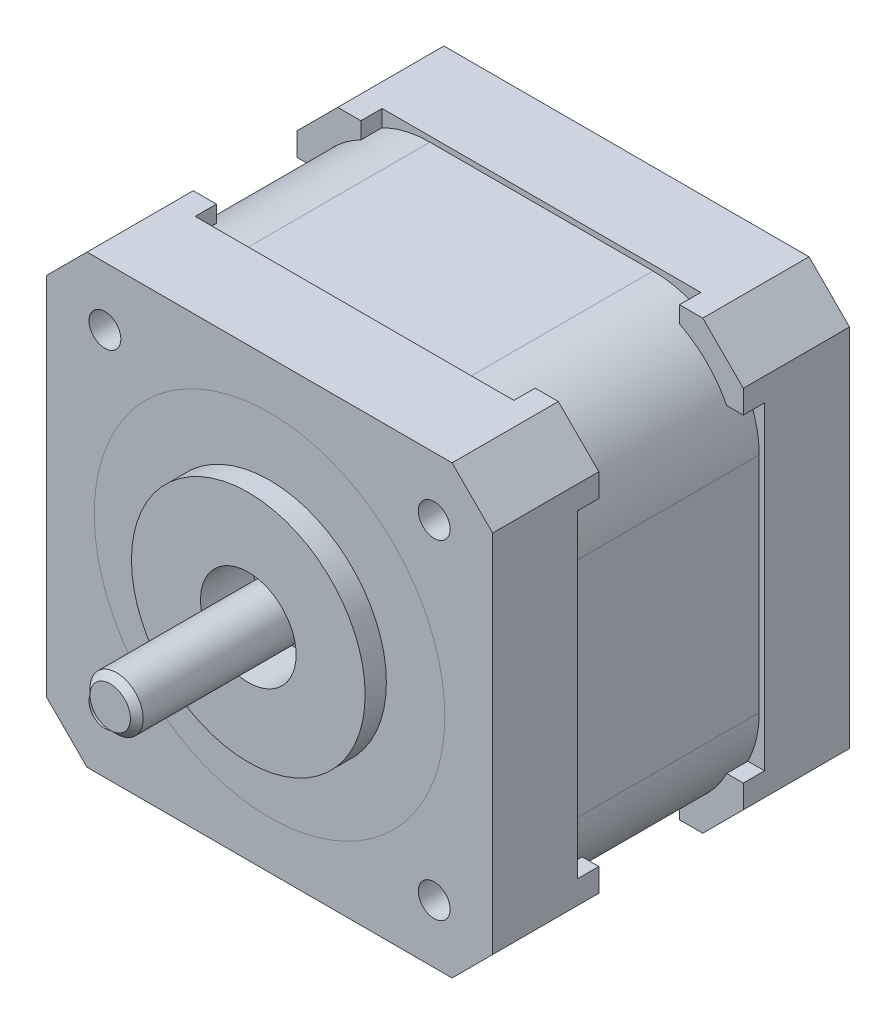
SolidWorks part; units mm, degrees
note: The reader was unsure of these and kept them because the rebuilt part matched: shared geometry of "Croquis4<4>", "Croquis5<3>", "Croquis5<4>", "Croquis5<5>".
ref_plane "Alzado" through (0, 0, 0) normal (0, 0, 1) x (1, 0, 0)
ref_plane "Planta" through (0, 0, 0) normal (0, 1, 0) x (1, 0, 0)
ref_plane "Vista lateral" through (0, 0, 0) normal (1, 0, 0) x (0, 0, -1)
sketch "Croquis1" plane through (0, 0, 0) normal (0, 0, 1) x (1, 0, 0)
  line L2 (0, 15.5) -> (-15.5, 15.5) construction
  line L3 (-15.5, -15.5) -> (-15.5, 15.5) construction
  line L4 (-17.1838, 21) -> (-21, 17.1838)
  line L5 (15.5, -15.5) -> (15.5, 15.5) construction
  line L6 (0, 21) -> (0, -21) construction
  line L7 (-21, 0) -> (21, 0) construction
  line L8 (21, 17.1838) -> (21, -17.1838)
  line L9 (17.1838, 21) -> (21, 17.1838)
  line L10 (0, -15.5) -> (-15.5, -15.5) construction
  line L11 (17.1838, -21) -> (-17.1838, -21)
  line L12 (17.1838, -21) -> (21, -17.1838)
  line L13 (-17.1838, -21) -> (-21, -17.1838)
  line L16 (17.1838, 21) -> (-17.1838, 21)
  line L18 (-21, 17.1838) -> (-21, -17.1838)
  circle A0 centre (-15.5, 15.5) radius 3
  circle A1 centre (15.5, 15.5) radius 3
  circle A2 centre (15.5, -15.5) radius 3
  circle A3 centre (-15.5, -15.5) radius 3
  point P1 (-21, 21)
  point P23 (21, 21)
  point P25 (0, 0)
  point P26 (15.5, 0)
  point P27 (-15.5, 0)
  point P34 (21, -21)
  point P35 (-21, -21)
  dimension "D4" = 6
  dimension "D2" = 31
  dimension "D3" = 15.5
  dimension "D5" = 54
  dimension "D6" = 42
  dimension "D1" = 42
extrude "Saliente-Extruir1" add sketch "Croquis1" along normal mid plane 33.6 contours L16 L4 L18 L13 L11 L12 L8 L9
sketch "Croquis2" plane through (0, 0, 16.8) normal (0, 0, 1) x (1, 0, 0)
  line L0 (21, -15) -> (-21, -15)
  line L1 (21, -15) -> (21, 15)
  line L2 (-21, -15) -> (-21, 15)
  line L3 (21, 15) -> (-21, 15)
  line L4 (21, -15) -> (-21, 15) construction
  line L5 (-21, -15) -> (21, 15) construction
  line L6 (-21, 17.1838) -> (-21, -17.1838) construction
  line L7 (17.1838, 21) -> (-17.1838, 21) construction
  line L8 (15, -21) -> (-15, -21)
  line L9 (15, -21) -> (15, 21)
  line L10 (15, 21) -> (-15, 21)
  line L11 (-15, -21) -> (-15, 21)
  line L12 (15, -21) -> (-15, 21) construction
  line L13 (15, 21) -> (-15, -21) construction
  point P1 (0, 0)
  point P3 (0, 0)
  line M10 (17.1838, 21) -> (-17.1838, 21)
  line M12 (-21, 17.1838) -> (-21, -17.1838)
  line M14 (-17.1838, -21) -> (17.1838, -21)
  line M16 (21, -17.1838) -> (21, 17.1838)
  dimension "D1" = 30
extrude "Cortar-Extruir1" cut sketch "Croquis2" against normal offset from surface (17.6 mm away) 8 from offset 8 contours L11 L3 L9 M10 | L11 L0 L9 L3 | L9 L0 L3 M16 | L11 L9 L0 M14 | L0 L11 L3 M12 up to face at (0, 0, -16.8) offset against normal yes
sketch "Croquis3" plane through (0, 0, -16.8) normal (0, 0, -1) x (-1, 0, 0)
  line L8 (-17.1838, 21) -> (-21, 17.1838)
  line L9 (-21, 17.1838) -> (-21, -17.1838)
  line L10 (-21, -17.1838) -> (-17.1838, -21)
  line L11 (-17.1838, -21) -> (17.1838, -21)
  line L12 (17.1838, -21) -> (21, -17.1838)
  line L13 (21, -17.1838) -> (21, 17.1838)
  line L14 (21, 17.1838) -> (17.1838, 21)
  line L15 (17.1838, 21) -> (-17.1838, 21)
  line L16 (-17.1838, 21) -> (-21, 17.1838)
  line L17 (-21, 17.1838) -> (-21, -17.1838)
  line L18 (-21, -17.1838) -> (-17.1838, -21)
  line L19 (-17.1838, -21) -> (17.1838, -21)
  line L20 (17.1838, -21) -> (21, -17.1838)
  line L21 (21, -17.1838) -> (21, 17.1838)
  line L22 (21, 17.1838) -> (17.1838, 21)
  line L23 (17.1838, 21) -> (-17.1838, 21)
  dimension "D1" = 0
extrude "Cortar-Extruir2" cut sketch "Croquis3" against normal offset from surface (13.6 mm away) 10 from offset 10 up to face at (0, 0, 16.8) offset against normal yes
sketch "Croquis4" plane through (0, 0, 16.8) normal (0, 0, 1) x (1, 0, 0)
  line L2 (-20.5, 10.5) -> (-20.5, -10.5)
  line L3 (10.5, 20.5) -> (-10.5, 20.5)
  line L4 (17.1838, 21) -> (-17.1838, 21) construction
  line L5 (-21, 17.1838) -> (-21, -17.1838) construction
  line L6 (0, -1000) -> (0, 49000) construction
  line L7 (-1000, 0) -> (49000, 0) construction
  line L8 (20.5, 10.5) -> (20.5, -10.5)
  line L9 (10.5, -20.5) -> (-10.5, -20.5)
  arc A4 (-10.5, 20.5) -> (-20.5, 10.5) centre (-10.5, 10.5) ccw
  arc A5 (10.5, 20.5) -> (20.5, 10.5) centre (10.5, 10.5) cw
  arc A6 (10.5, -20.5) -> (20.5, -10.5) centre (10.5, -10.5) ccw
  arc A7 (-10.5, -20.5) -> (-20.5, -10.5) centre (-10.5, -10.5) cw
  dimension "D1" = 10
  dimension "D3" = 0.5
  dimension "D4" = 0.5
extrude "Cortar-Extruir3" cut sketch "Croquis4<4>" against normal up to surface (17.6 mm away) from surface
sketch "Croquis4<4>" plane through (0, 0, 16.8) normal (0, 0, 1) x (1, 0, 0) same geometry as "Croquis4"
extrude "Saliente-Extruir2" add sketch "Croquis4" against normal up to next from surface separate body contours A5 L8 A6 L9 A7 L2 A4 L3
sketch "Croquis5" plane through (0, 0, 16.8) normal (0, 0, 1) x (1, 0, 0)
  circle A0 centre (0, 0) radius 16.5
  circle A1 centre (0, 0) radius 11
  circle A2 centre (0, 0) radius 4.5
  circle A3 centre (0, 0) radius 2.5
  dimension "D1" = 33
  dimension "22" = 22
  dimension "D3" = 9
  dimension "D4" = 5
extrude "Cortar-Extruir4" cut sketch "Croquis5" against normal blind 3 contours A0 A1 | A1 A2 | A2 A3 | A3
extrude "Saliente-Extruir3" add sketch "Croquis5<3>" against normal up to body (3 mm away) contours A0 A1
sketch "Croquis5<3>" plane through (0, 0, 16.8) normal (0, 0, 1) x (1, 0, 0) same geometry as "Croquis5"
extrude "Saliente-Extruir4" add sketch "Croquis5<4>" along normal blind 5 from surface at -3 separate body contours A1 A2 starting at face at (16.5, 0, 13.8)
sketch "Croquis5<4>" plane through (0, 0, 16.8) normal (0, 0, 1) x (1, 0, 0) same geometry as "Croquis5"
extrude "Saliente-Extruir5" add sketch "Croquis5<5>" along normal blind 18 from surface at -3 contours A3 starting at face at (16.5, 0, 13.8)
sketch "Croquis5<5>" plane through (0, 0, 16.8) normal (0, 0, 1) x (1, 0, 0) same geometry as "Croquis5"
chamfer "Chaflán1" distance 0.6 angle 45 1 edges at (2.5, 0, 31.8)
sketch "Croquis6" plane through (0, 0, 16.8) normal (0, 0, 1) x (1, 0, 0)
  line L0 (15.5, -15.5) -> (15.5, 15.5) construction
  line L1 (15.5, -15.5) -> (-15.5, -15.5) construction
  line L2 (15.5, 15.5) -> (-15.5, 15.5) construction
  line L3 (-15.5, -15.5) -> (-15.5, 15.5) construction
  line L4 (15.5, -15.5) -> (-15.5, 15.5) construction
  line L5 (15.5, 15.5) -> (-15.5, -15.5) construction
  circle A0 centre (-15.5, 15.5) radius 1.5
  circle A1 centre (15.5, -15.5) radius 1.5
  circle A2 centre (15.5, 15.5) radius 1.5
  circle A3 centre (-15.5, -15.5) radius 1.5
  point P3 (0, 0)
  dimension "D2" = 3
  dimension "D1" = 31
extrude "Cortar-Extruir5" cut sketch "Croquis6" against normal blind 6 contours A3 | A1 | A2 | A0
sketch "Sketch1" plane through (0, 0, 16.8) normal (0, 0, 1) x (1, 0, 0)
  line L8 (21, 17.1838) -> (17.1838, 21)
  line L9 (17.1838, 21) -> (-17.1838, 21)
  line L10 (-17.1838, 21) -> (-21, 17.1838)
  line L11 (-21, 17.1838) -> (-21, -17.1838)
  line L12 (-21, -17.1838) -> (-17.1838, -21)
  line L13 (-17.1838, -21) -> (17.1838, -21)
  line L14 (17.1838, -21) -> (21, -17.1838)
  line L15 (21, -17.1838) -> (21, 17.1838)
  line L16 (21, 17.1838) -> (17.1838, 21)
  line L17 (17.1838, 21) -> (-17.1838, 21)
  line L18 (-17.1838, 21) -> (-21, 17.1838)
  line L19 (-21, 17.1838) -> (-21, -17.1838)
  line L20 (-21, -17.1838) -> (-17.1838, -21)
  line L21 (-17.1838, -21) -> (17.1838, -21)
  line L22 (17.1838, -21) -> (21, -17.1838)
  line L23 (21, -17.1838) -> (21, 17.1838)
  circle A1 centre (0, 0) radius 16.5
  circle A2 centre (0, 0) radius 16.5
  dimension "D1" = 0
  dimension "D2" = 0
